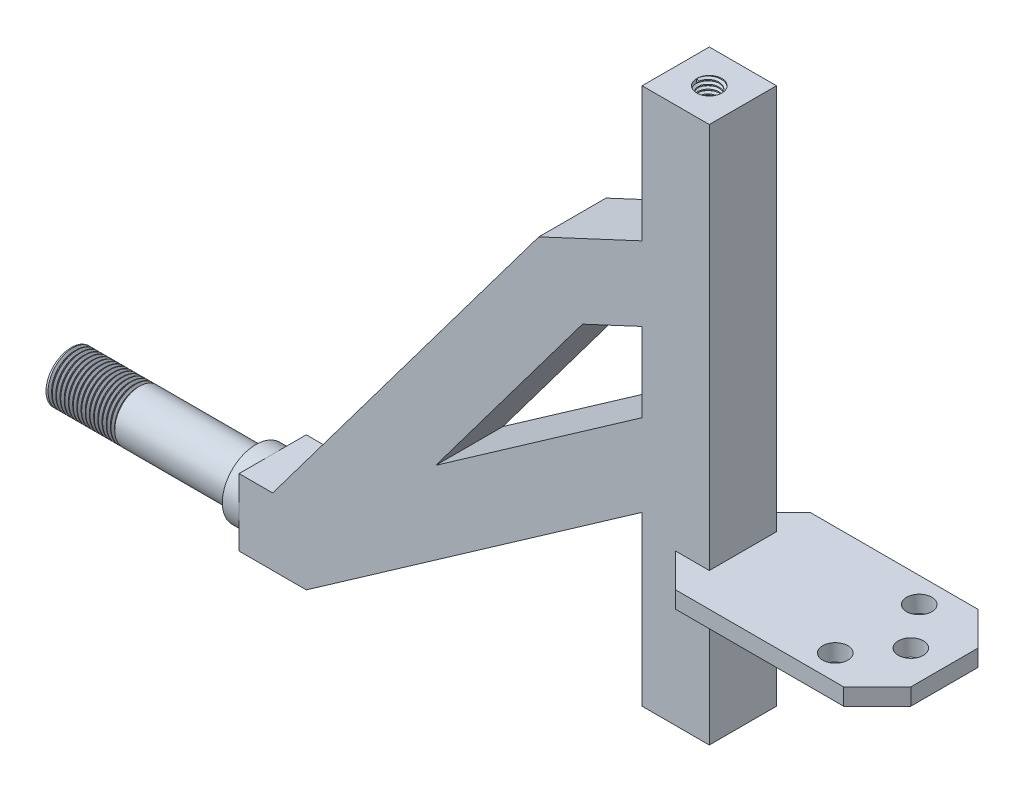
SolidWorks part; units mm, degrees
material "Plain Carbon Steel"
ref_plane "Front Plane" through (0, 0, 0) normal (0, 0, 1) x (1, 0, 0)
ref_plane "Top Plane" through (0, 0, 0) normal (0, 1, 0) x (1, 0, 0)
ref_plane "Right Plane" through (0, 0, 0) normal (1, 0, 0) x (0, 0, -1)
sketch "Sketch1" plane through (0, 0, 0) normal (0, 1, 0) x (1, 0, 0)
  line L1 (12.7, -12.7) -> (-12.7, -12.7)
  line L2 (12.7, -12.7) -> (12.7, 12.7)
  line L3 (12.7, 12.7) -> (-12.7, 12.7)
  line L4 (-12.7, -12.7) -> (-12.7, 12.7)
  line L5 (12.7, -12.7) -> (-12.7, 12.7) construction
  line L6 (12.7, 12.7) -> (-12.7, -12.7) construction
  line L7 (10.16, -10.16) -> (-10.16, -10.16)
  line L8 (10.16, -10.16) -> (10.16, 10.16)
  line L9 (10.16, 10.16) -> (-10.16, 10.16)
  line L10 (-10.16, -10.16) -> (-10.16, 10.16)
  line L11 (10.16, -10.16) -> (-10.16, 10.16) construction
  line L12 (10.16, 10.16) -> (-10.16, -10.16) construction
  point P0 (0, 0)
  point P5 (0, 0)
  dimension "D1" = 2.54
  dimension "1" = 25.4
extrude "Sq_Tb Extrude" add sketch "Sketch1" along normal blind 203.2
sketch "Sketch3" plane through (0, 203.2, 0) normal (0, 1, 0) x (1, 0, 0)
  line L1 (10.16, -10.16) -> (-10.16, -10.16)
  line L2 (10.16, -10.16) -> (10.16, 10.16)
  line L3 (10.16, 10.16) -> (-10.16, 10.16)
  line L4 (-10.16, -10.16) -> (-10.16, 10.16)
  line L5 (10.16, -10.16) -> (-10.16, 10.16) construction
  line L6 (10.16, 10.16) -> (-10.16, -10.16) construction
  circle A0 centre (0, 0) radius 4.7625
  point P0 (0, 0)
  dimension "D1" = 9.525
extrude "End Caps" add sketch "Sketch3" against normal blind 6.35
ref_plane "Mid-Plane" through (0, 101.6, 0) normal (0, 1, 0) x (1, 0, 0)
mirror "End Cap Mirror" about plane through (0, 101.6, 0) normal (0, 1, 0) of "End Caps"
thread "Top Thread" pitch 1.5875 method extrude profile "Thread Profile1" start angle 0, offset 0, length 0, pitch 1.5875, diameter 9.525
ref_plane "Plane2" through (-4.7625, 203.2, 0) normal (0, 0, 1) x (-1, 0, 0)
sketch "Thread Profile1" plane through (-4.7625, 203.2, 0) normal (0, 0, 1) x (-1, 0, 0)
  line L0 (0, 0) -> (0, 1.5875) construction
  line L11 (0, 0) -> (0, 1.3891)
  line L12 (0, 1.3891) -> (-0.8593, 0.893)
  line L13 (-0.8593, 0.893) -> (-0.8593, 0.4961)
  line L15 (-0.8593, 0.4961) -> (0, 0)
  line L17 (-0.8593, 0.6945) -> (0, 0.6945) construction
  point P2 (0, 0)
  dimension "Pitch" = 1.5875
  dimension "Profile_Angle" = 60
  dimension "Profile_Land" = 0.3969
  dimension "Profile_Height" = 0.8593
thread "Bottom Thread" pitch 1.5875 method extrude profile "Thread Profile2" start angle 0, offset 0, length 0, pitch 1.5875, diameter 9.525
ref_plane "Plane3" through (4.7625, 0, 0) normal (0, 0, 1) x (1, 0, 0)
sketch "Thread Profile2" plane through (4.7625, 0, 0) normal (0, 0, 1) x (1, 0, 0)
  line L0 (0, 0) -> (0, 1.5875) construction
  line L11 (0, 0) -> (0, 1.3891)
  line L12 (0, 1.3891) -> (-0.8593, 0.893)
  line L13 (-0.8593, 0.893) -> (-0.8593, 0.4961)
  line L15 (-0.8593, 0.4961) -> (0, 0)
  line L17 (-0.8593, 0.6945) -> (0, 0.6945) construction
  point P2 (0, 0)
  dimension "Pitch" = 1.5875
  dimension "Profile_Angle" = 60
  dimension "Profile_Land" = 0.3969
  dimension "Profile_Height" = 0.8593
sketch "Sketch9" plane through (0, 0, 0) normal (0, 0, 1) x (1, 0, 0)
  line L0 (-12.7, 152.4) -> (-51.7607, 134.1857)
  line L1 (-12.7, 203.2) -> (-12.7, 0) construction
  line L2 (-102.0804, 67.0928) -> (-81.7604, 51.8528) construction
  line L3 (-35.2589, 113.8548) -> (-12.7, 124.3742)
  line L4 (-12.7, 63.5) -> (-139.7, -25.4)
  line L5 (-90.7453, 39.873) -> (-12.7, 94.5047)
  line L6 (-12.7, 94.5047) -> (-12.7, 63.5)
  line L8 (-51.7607, 134.1857) -> (-152.4, 0)
  line L9 (-12.7, 152.4) -> (-12.7, 124.3742)
  line L10 (-139.7, -25.4) -> (-35.2589, 113.8548)
  line L11 (-139.7, -25.4) -> (-165.1, -25.4)
  line L12 (-165.1, -25.4) -> (-165.1, 0)
  line L13 (-165.1, 0) -> (-152.4, 0)
  line L14 (-32.2304, 143.2928) -> (-21.4959, 120.2726) construction
  line L15 (-165.1, -12.7) -> (0, -12.7) construction
  line L16 (0, -12.7) -> (0, 0) construction
  line L17 (-12.7, 203.2) -> (12.7, 203.2) construction
  line L18 (-12.7, 0) -> (12.7, 0) construction
  line L19 (-51.7226, 67.1888) -> (-37.1567, 46.3803) construction
  dimension "D1" = 25.4
  dimension "D2" = 12.7
  dimension "D3" = 50.8
  dimension "D4" = 63.5
  dimension "D5" = 12.7
  dimension "D6" = 152.4
  dimension "D7" = 115
  dimension "D8" = 25.4
extrude "Sq_Tb Angles" add sketch "Sketch9" along normal blind 12.7 and the other way blind 12.7 contours L13 L12 L11 L10 L3 L9 L0 L8 | L10 L4 L6 L5 region at (-89.8217, 61.3024, 0) region at (-64.9353, 41.2039, 0)
sketch "Sketch11" plane through (0, 0, 0) normal (0, 0, 1) x (1, 0, 0)
  line L0 (-165.1, -12.7) -> (-241.3, -12.7)
  line L1 (-165.1, -25.4) -> (-165.1, 0) construction
  line L2 (-241.3, -12.7) -> (-241.3, -3.175)
  line L3 (-241.3, -3.175) -> (-171.45, -3.175)
  line L4 (-171.45, -3.175) -> (-171.45, 0)
  line L5 (-171.45, 0) -> (-165.1, 0)
  line L6 (-165.1, 0) -> (-165.1, -12.7)
  dimension "D1" = 12.7
  dimension "D2" = 9.525
  dimension "D3" = 6.35
  dimension "D4" = 76.2
revolve "Wheel Rod" add sketch "Sketch11" angle 360 about L0
thread "Wheel Threads" pitch 1.5875 method cut profile "Thread Profile3" start angle 0, offset 0, length 25.4, pitch 1.5875, diameter 19.05
ref_plane "Plane4" through (-241.3, -12.7, -9.525) normal (0, -1, 0) x (0, 0, -1)
sketch "Thread Profile3" plane through (-241.3, -12.7, -9.525) normal (0, -1, 0) x (0, 0, -1)
  line L0 (0, 0) -> (0, 1.5875) construction
  line L11 (0, 0) -> (0, 1.3891)
  line L12 (0, 1.3891) -> (-0.8593, 0.893)
  line L13 (-0.8593, 0.893) -> (-0.8593, 0.4961)
  line L15 (-0.8593, 0.4961) -> (0, 0)
  line L17 (-0.8593, 0.6945) -> (0, 0.6945) construction
  point P2 (0, 0)
  dimension "Pitch" = 1.5875
  dimension "Profile_Angle" = 60
  dimension "Profile_Land" = 0.3969
  dimension "Profile_Height" = 0.8593
ref_plane "Tie-Rod Mount Plane" through (0, 50.8, 0) normal (0, 1, 0) x (1, 0, 0)
sketch "Sketch15" plane through (0, 50.8, 0) normal (0, 1, 0) x (1, 0, 0)
  line L0 (0, 12.7) -> (12.7, 25.4)
  line L1 (12.7, 12.7) -> (-12.7, 12.7) construction
  line L2 (12.7, 25.4) -> (76.2, 25.4)
  line L3 (0, -12.7) -> (12.7, -25.4)
  line L4 (-12.7, -12.7) -> (12.7, -12.7) construction
  line L5 (0, 12.7) -> (12.7, 12.7)
  line L6 (12.7, -12.7) -> (12.7, 12.7) construction
  line L7 (12.7, 12.7) -> (12.7, -12.7)
  line L8 (12.7, -12.7) -> (0, -12.7)
  line L9 (12.7, -25.4) -> (76.2, -25.4)
  line L10 (76.2, -25.4) -> (76.2, 25.4) construction
  line L11 (12.7, 25.4) -> (12.7, 12.7) construction
  line L12 (12.7, -12.7) -> (12.7, -25.4) construction
  line L13 (76.2, 25.4) -> (88.9, 12.7)
  line L14 (88.9, 12.7) -> (88.9, -12.7)
  line L15 (88.9, -12.7) -> (76.2, -25.4)
  line L16 (12.7, 0) -> (88.9, 0) construction
  dimension "D1" = 12.7
  dimension "D2" = 76.2
  dimension "D3" = 12.7
extrude "Tie-Rod Mount Plate" add sketch "Sketch15" along normal blind 6.35
sketch "Sketch16" plane through (0, 57.15, 0) normal (0, 1, 0) x (1, 0, 0)
  line L0 (12.7, 0) -> (63.5, 0) construction
  line L1 (12.7, -12.7) -> (12.7, 12.7) construction
  line L2 (63.5, 0) -> (63.5, 15.875) construction
  line L3 (12.7, 0) -> (76.2, 0) construction
  circle A0 centre (63.5, 15.875) radius 4.7625
  circle A1 centre (63.5, -15.875) radius 4.7625
  circle A2 centre (76.2, 0) radius 4.7625
  dimension "D1" = 50.8
  dimension "D3" = 9.525
  dimension "D2" = 15.875
  dimension "D4" = 63.5
extrude "Tie-Rod Mount Hole" cut sketch "Sketch16" against normal through all
